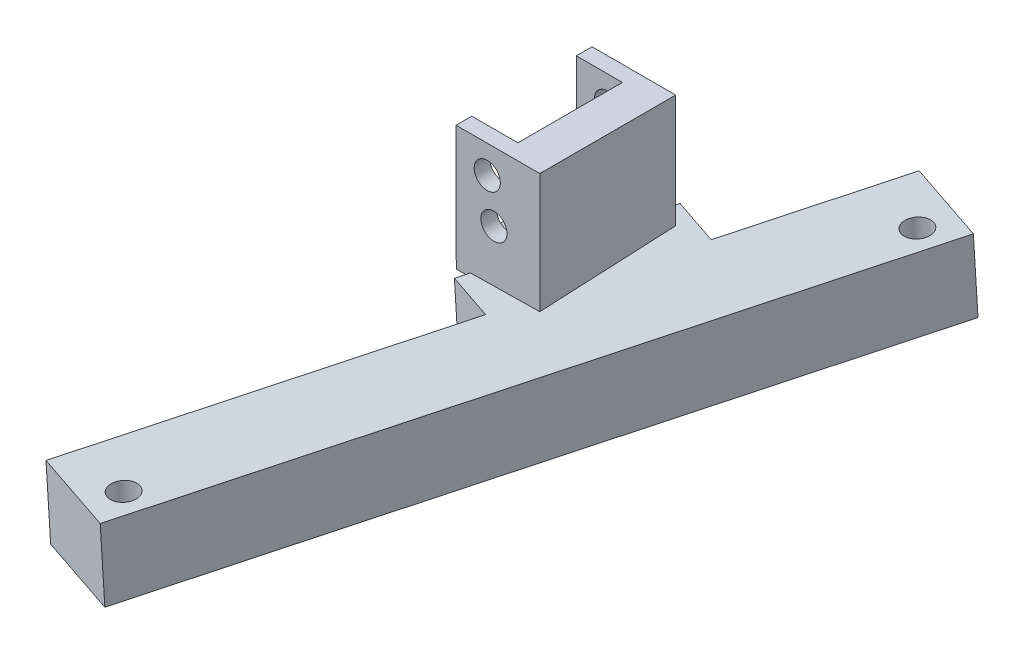
SolidWorks part; units mm, degrees
ref_plane "Front Plane" through (0, 0, 0) normal (0, 0, 1) x (1, 0, 0)
ref_plane "Top Plane" through (0, 0, 0) normal (0, 1, 0) x (1, 0, 0)
ref_plane "Right Plane" through (0, 0, 0) normal (1, 0, 0) x (0, 0, -1)
sketch "Sketch1" plane through (0, 0, 0) normal (0, 0, 1) x (1, 0, 0)
  line L0 (427.4923, 249.3739) -> (458.8626, 254.5214) construction
  line L1 (448.4353, 278.7761) -> (468.7553, 278.7761)
  line L2 (448.4353, 278.7761) -> (448.4353, 250.4861)
  line L3 (448.4353, 250.4861) -> (468.7553, 250.4861)
  line L4 (468.7553, 278.7761) -> (468.7553, 250.4861)
  line L5 (427.4923, 249.3739) -> (458.8626, 254.5214)
  line L6 (448.4353, 252.8104) -> (458.8626, 254.5214)
  arc A0 (461.3669, 277.5061) -> (454.7498, 279.5862) centre (455.9966, 271.9877) ccw construction
  arc A1 (463.4772, 270.1621) -> (461.3669, 277.5061) centre (455.9966, 271.9877) ccw construction
  arc A2 (463.4772, 270.1621) -> (464.1208, 266.2396) centre (468.4124, 268.9577) ccw construction
  arc A3 (464.4679, 258.6072) -> (464.1208, 266.2396) centre (457.6159, 262.1197) ccw construction
  arc A4 (458.8626, 254.5214) -> (464.4679, 258.6072) centre (457.6159, 262.1197) ccw construction
  arc A5 (461.3669, 277.5061) -> (454.7498, 279.5862) centre (455.9966, 271.9877) ccw
  arc A6 (463.4772, 270.1621) -> (461.3669, 277.5061) centre (455.9966, 271.9877) ccw
  arc A7 (463.4772, 270.1621) -> (464.1208, 266.2396) centre (468.4124, 268.9577) ccw
  arc A8 (464.4679, 258.6072) -> (464.1208, 266.2396) centre (457.6159, 262.1197) ccw
  arc A9 (458.8626, 254.5214) -> (464.4679, 258.6072) centre (457.6159, 262.1197) ccw
  arc A10 (458.8626, 254.5214) -> (464.4679, 258.6072) centre (457.6159, 262.1197) ccw
  arc A11 (464.4679, 258.6072) -> (464.1208, 266.2396) centre (457.6159, 262.1197) ccw
  arc A12 (464.1208, 266.2396) -> (463.4772, 270.1621) centre (468.4124, 268.9577) cw
  arc A13 (463.4772, 270.1621) -> (461.3669, 277.5061) centre (455.9966, 271.9877) ccw
  arc A14 (461.3669, 277.5061) -> (459.6312, 278.7761) centre (455.9966, 271.9877) ccw
  circle A15 centre (457.6159, 262.1197) radius 3.175
  circle A16 centre (455.9966, 271.9877) radius 3.175
  dimension "D1" = 4.0353
  dimension "D2" = 1.27
  dimension "D3" = 20.32
  dimension "D4" = 10.16
extrude "Boss-Extrude1" add sketch "Sketch1" against normal blind 29.21 contours A9 L5 L2 L3 L4 L1 A5 A6 A7 A8 region at (464.1933, 278.4278, 0)
sketch "Sketch2" plane through (0, 0, 0) normal (0, 0, 1) x (1, 0, 0)
  line L0 (448.4353, 252.8104) -> (448.4353, 278.7761)
  line L1 (448.4353, 278.7761) -> (468.7553, 278.7761)
  line L2 (468.7553, 278.7761) -> (468.7553, 250.4861)
  line L3 (468.7553, 250.4861) -> (448.4353, 250.4861)
  line L4 (448.4353, 250.4861) -> (448.4353, 252.8104)
  circle A0 centre (455.9966, 271.9877) radius 3.175
  circle A1 centre (457.6159, 262.1197) radius 3.175
  dimension "D1" = 6.35
  dimension "D2" = 6.35
extrude "Boss-Extrude2" add sketch "Sketch2" along normal blind 3.81
sketch "Sketch3" plane through (0, 0, -25.4) normal (0, 0, -1) x (-1, 0, 0)
  line L0 (-448.4353, 252.8104) -> (-458.8626, 254.5214) construction
  line L1 (-448.4353, 252.8104) -> (-458.8626, 254.5214)
  line L2 (-448.4353, 252.8104) -> (-448.4353, 278.7761)
  line L3 (-448.4353, 278.7761) -> (-459.6312, 278.7761)
  line L4 (-458.8626, 254.5214) -> (-448.4353, 252.8104)
  arc A0 (-464.1208, 266.2396) -> (-458.8626, 254.5214) centre (-457.6159, 262.1197) ccw construction
  arc A1 (-464.1208, 266.2396) -> (-463.4772, 270.1621) centre (-468.4124, 268.9577) ccw construction
  arc A2 (-459.6312, 278.7761) -> (-463.4772, 270.1621) centre (-455.9966, 271.9877) ccw construction
  arc A3 (-464.1208, 266.2396) -> (-458.8626, 254.5214) centre (-457.6159, 262.1197) ccw
  arc A4 (-464.1208, 266.2396) -> (-463.4772, 270.1621) centre (-468.4124, 268.9577) ccw
  arc A5 (-459.6312, 278.7761) -> (-463.4772, 270.1621) centre (-455.9966, 271.9877) ccw
  arc A6 (-459.6312, 278.7761) -> (-463.4772, 270.1621) centre (-455.9966, 271.9877) ccw
  arc A7 (-463.4772, 270.1621) -> (-464.1208, 266.2396) centre (-468.4124, 268.9577) cw
  arc A8 (-464.1208, 266.2396) -> (-458.8626, 254.5214) centre (-457.6159, 262.1197) ccw
  circle A9 centre (-457.6159, 262.1197) radius 3.175
  circle A10 centre (-455.9966, 271.9877) radius 3.175
  line M4 (-423.8853, 271.3557) -> (-461.3669, 277.5061)
  arc M5 (-461.3669, 277.5061) -> (-463.4772, 270.1621) centre (-455.9966, 271.9877) ccw
  arc M6 (-463.4772, 270.1621) -> (-464.1208, 266.2396) centre (-468.4124, 268.9577) cw
  arc M7 (-464.1208, 266.2396) -> (-464.4679, 258.6072) centre (-457.6159, 262.1197) ccw
  line M8 (-464.4679, 258.6072) -> (-424.8406, 252.1047)
  circle M9 centre (-457.6159, 262.1197) radius 3.175
  circle M10 centre (-455.9966, 271.9877) radius 3.175
  dimension "D1" = 6.35
  dimension "D2" = 6.35
extrude "Boss-Extrude3" add sketch "Sketch3" along normal up to surface (3.81 mm away) contours L2 M8 M4 M5 M6 M7 M9 M10 | A3 L1 L2 M8 | L3 A5 L2 M4 region at (455.7154, 255.665, -25.4) region at (456.0581, 266.5213, -25.4) region at (453.6849, 277.5014, -25.4) up to face at (460.587, 262.6797, -29.21)
ref_plane "Plane1" through (-3.842, 241.8411, 11.4068) normal (-0.0159, 0.9988, 0.0471) x (0.9999, 0.0158, 0.0007)
sketch "Sketch4" plane through (-3.842, 241.8411, 11.4068) normal (-0.0159, 0.9988, 0.0471) x (0.9999, 0.0158, 0.0007)
  line L0 (459.2158, -85.5005) -> (512.6671, 73.3898)
  line L1 (512.6671, 73.3898) -> (492.8082, 80.0704)
  line L2 (492.8082, 80.0704) -> (480.0779, 42.228)
  line L3 (480.0779, 42.228) -> (468.6402, 46.0757)
  line L4 (468.6402, 46.0757) -> (454.8306, 5.0251)
  line L5 (454.8306, 5.0251) -> (466.2683, 1.1774)
  line L6 (466.2683, 1.1774) -> (439.3569, -78.8198)
  line L7 (439.3569, -78.8198) -> (459.2158, -85.5005)
  circle A0 centre (455.6747, -76.2696) radius 3.175
  circle A1 centre (504.2669, 68.1761) radius 3.175
  dimension "D6" = 39.9263
  dimension "D8" = 6.35
  dimension "D10" = 6.35
  dimension "D2" = 7.62
  dimension "D3" = 7.62
  dimension "D4" = 167.64
  dimension "D5" = 20.9525
  dimension "D7" = 84.4025
  dimension "D9" = 17.0596
  dimension "D11" = 20.9525
  dimension "D12" = 33.02
extrude "Boss-Extrude4" add sketch "Sketch4" against normal up to surface (17.9165 mm away)
sketch "Sketch5" plane through (0, 0, 3.81) normal (0, 0, 1) x (1, 0, 0)
  line L0 (468.7553, 250.4861) -> (448.5605, 250.4861)
  line L1 (448.4353, 250.4861) -> (468.7553, 250.4861) construction
  line L2 (448.5605, 250.4861) -> (448.5605, 248.529)
  line L3 (448.5605, 248.529) -> (468.7553, 248.3932)
  line L4 (468.7553, 248.3932) -> (468.7553, 250.4861)
extrude "Boss-Extrude5" add sketch "Sketch5" against normal up to surface (33.02 mm away) up to face at (460.0754, 260.1605, -29.21)
